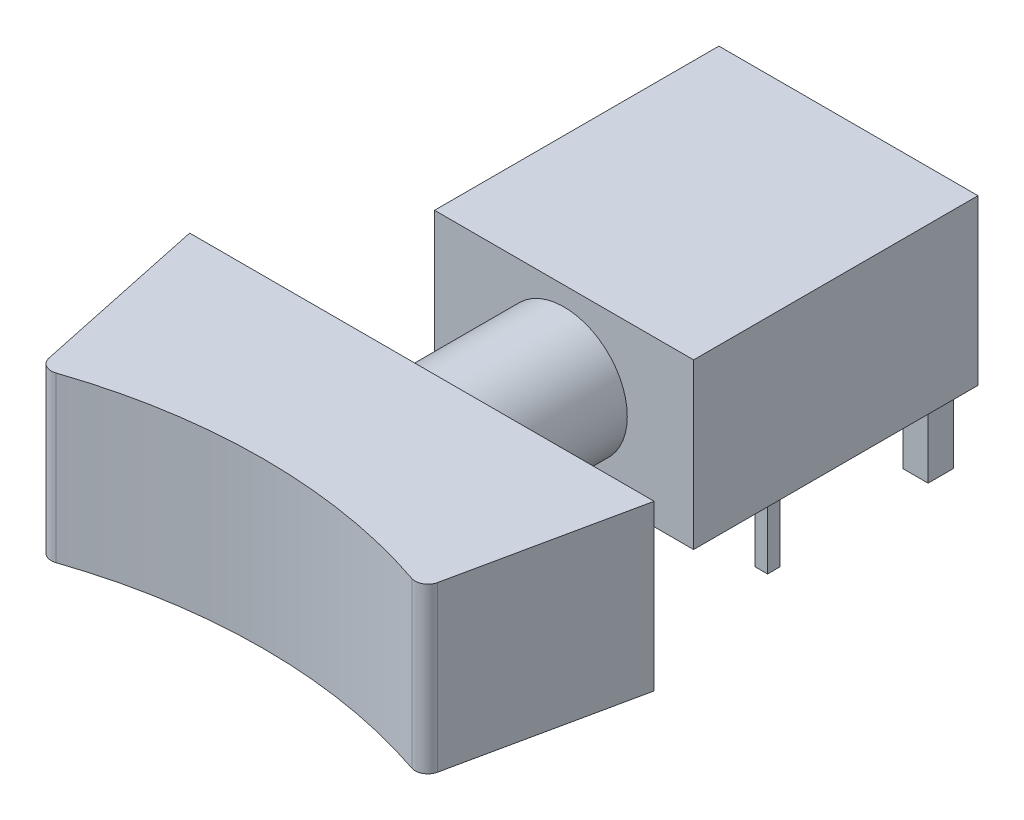
SolidWorks part; units mm, degrees
ref_plane "Front Plane" through (0, 0, 0) normal (0, 0, 1) x (1, 0, 0)
ref_plane "Top Plane" through (0, 0, 0) normal (0, 1, 0) x (1, 0, 0)
ref_plane "Right Plane" through (0, 0, 0) normal (1, 0, 0) x (0, 0, -1)
sketch "Sketch1" plane through (0, 0, 0) normal (0, 1, 0) x (1, 0, 0)
  line L1 (-4.1, 4.5) -> (4.1, 4.5)
  line L2 (-4.1, 4.5) -> (-4.1, -4.5)
  line L3 (-4.1, -4.5) -> (4.1, -4.5)
  line L4 (4.1, 4.5) -> (4.1, -4.5)
  line L5 (-4.1, 4.5) -> (4.1, -4.5) construction
  line L6 (-4.1, -4.5) -> (4.1, 4.5) construction
  point P0 (0, 0)
  dimension "D1" = 9
  dimension "D2" = 8.2
extrude "Boss-Extrude1" add sketch "Sketch1" along normal blind 5.2
sketch "Sketch2" plane through (0, 0, 0) normal (0, -1, 0) x (1, 0, 0)
  line L0 (-2.54, 0.6) -> (2.54, 0.6) construction
  line L1 (-2.74, 0.8) -> (-2.34, 0.8)
  line L2 (-2.74, 0.8) -> (-2.74, 0.4)
  line L3 (-2.74, 0.4) -> (-2.34, 0.4)
  line L4 (-2.34, 0.8) -> (-2.34, 0.4)
  line L5 (-2.74, 0.8) -> (-2.34, 0.4) construction
  line L6 (-2.74, 0.4) -> (-2.34, 0.8) construction
  line L7 (2.34, 0.8) -> (2.74, 0.8)
  line L8 (2.34, 0.8) -> (2.34, 0.4)
  line L9 (2.34, 0.4) -> (2.74, 0.4)
  line L10 (2.74, 0.8) -> (2.74, 0.4)
  line L11 (2.34, 0.8) -> (2.74, 0.4) construction
  line L12 (2.34, 0.4) -> (2.74, 0.8) construction
  line L13 (-2.94, -4.08) -> (-2.14, -4.08)
  line L14 (-2.94, -4.08) -> (-2.94, -4.88)
  line L15 (-2.94, -4.88) -> (-2.14, -4.88)
  line L16 (-2.14, -4.08) -> (-2.14, -4.88)
  line L17 (-2.94, -4.08) -> (-2.14, -4.88) construction
  line L18 (-2.94, -4.88) -> (-2.14, -4.08) construction
  line L19 (-0.4, -4.08) -> (0.4, -4.08)
  line L20 (-0.4, -4.08) -> (-0.4, -4.88)
  line L21 (-0.4, -4.88) -> (0.4, -4.88)
  line L22 (0.4, -4.08) -> (0.4, -4.88)
  line L23 (-0.4, -4.08) -> (0.4, -4.88) construction
  line L24 (-0.4, -4.88) -> (0.4, -4.08) construction
  line L25 (2.14, -4.08) -> (2.94, -4.08)
  line L26 (2.14, -4.08) -> (2.14, -4.88)
  line L27 (2.14, -4.88) -> (2.94, -4.88)
  line L28 (2.94, -4.08) -> (2.94, -4.88)
  line L29 (2.14, -4.08) -> (2.94, -4.88) construction
  line L30 (2.14, -4.88) -> (2.94, -4.08) construction
  line L32 (-4.1, 4.5) -> (4.1, 4.5) construction
  point P0 (-2.54, 0.6)
  point P5 (2.54, 0.6)
  point P10 (-2.54, -4.48)
  point P15 (0, -4.48)
  point P20 (2.54, -4.48)
  point P25 (0, 0.6)
  line M25 (-4.1, -4.5) -> (4.1, -4.5)
  dimension "D1" = 2.54
  dimension "D2" = 2.54
  dimension "D3" = 5.08
  dimension "D4" = 0.8
  dimension "D5" = 0.4
  dimension "D6" = 3.9
  dimension "D7" = 5.08
extrude "Boss-Extrude2" add sketch "Sketch2" along normal blind 3.3
chamfer "Chamfer1" distance 0.1 angle 45 8 edges at (2.54, -3.3, 0.4) (2.34, -3.3, 0.6) (2.54, -3.3, 0.8) (2.74, -3.3, 0.6) (-2.54, -3.3, 0.4) (-2.74, -3.3, 0.6) (-2.54, -3.3, 0.8) (-2.34, -3.3, 0.6)
chamfer "Chamfer2" distance 0.25 angle 45 12 edges at (-2.54, -3.3, -4.88) (-2.94, -3.3, -4.48) (-2.54, -3.3, -4.08) (-2.14, -3.3, -4.48) (0, -3.3, -4.88) (-0.4, -3.3, -4.48) (0, -3.3, -4.08) (0.4, -3.3, -4.48) (2.54, -3.3, -4.88) (2.14, -3.3, -4.48) (2.54, -3.3, -4.08) (2.94, -3.3, -4.48)
extrude "Boss-Extrude3" add sketch "Sketch2<2>" against normal blind 3 contours L16 L14 L15 M25 | L22 L20 L21 M25 | L28 L26 L27 M25 region at (2.54, 0, -4.69) region at (0, 0, -4.69) region at (-2.54, 0, -4.69)
sketch "Sketch2<2>" plane through (0, 0, 0) normal (0, -1, 0) x (1, 0, 0) same geometry as "Sketch2"
fillet "Fillet1" radius 0.3 3 edges at (2.54, 3, -4.88) (0, 3, -4.88) (-2.54, 3, -4.88)
sketch "Sketch3" plane through (0, 0, 4.5) normal (0, 0, 1) x (1, 0, 0)
  line L0 (-4.1, 5.2) -> (-4.1, 0) construction
  circle A0 centre (0, 2.6) radius 2
  point P2 (0, 0)
  point P4 (0, 0)
  point P7 (-4.1, 2.6)
  dimension "D1" = 4
extrude "Boss-Extrude4" add sketch "Sketch3" along normal blind 4.5
sketch "Sketch4" plane through (0, 0, 9) normal (0, 0, 1) x (1, 0, 0)
  line L1 (-7.35, 5.2) -> (7.35, 5.2)
  line L2 (-7.35, 5.2) -> (-7.35, 0)
  line L3 (-7.35, 0) -> (7.35, 0)
  line L4 (7.35, 5.2) -> (7.35, 0)
  line L5 (-7.35, 5.2) -> (7.35, 0) construction
  line L6 (-7.35, 0) -> (7.35, 5.2) construction
  point P0 (0, 2.6)
  dimension "D1" = 5.2
  dimension "D2" = 14.7
extrude "Boss-Extrude5" add sketch "Sketch4" along normal offset from surface (6.1 mm away) 10.6 up to face at (2, 2.6, 4.5) offset beyond the face yes
sketch "Sketch5" plane through (0, 5.2, 0) normal (0, 1, 0) x (1, 0, 0)
  line L1 (-7.35, -9) -> (-6.0568, -15.1)
  line L2 (6.0568, -15.1) -> (7.35, -9)
  line L3 (-7.35, -15.1) -> (7.35, -15.1) construction
  line L4 (7.35, -9) -> (7.35, -15.1)
  line L5 (7.35, -15.1) -> (6.0568, -15.1)
  line L6 (-7.35, -9) -> (-7.35, -15.1)
  line L7 (-7.35, -15.1) -> (-6.0568, -15.1)
  line L8 (6.0568, -15.1) -> (-6.0568, -15.1)
  arc A0 (-6.0568, -15.1) -> (6.0568, -15.1) centre (0, -31.5536) cw
  point P3 (0, -14.0206)
  line M4 (-7.35, -9) -> (-7.35, -15.1)
  line M5 (-7.35, -15.1) -> (7.35, -15.1)
  line M6 (7.35, -15.1) -> (7.35, -9)
extrude "Cut-Extrude1" cut sketch "Sketch5" against normal through all contours L1 M4 M5 | A0 M5 | L2 M5 M6 region at (6.9189, 5.2, 13.0667) region at (0, 5.2, 14.6671) region at (-6.9189, 5.2, 13.0667)
fillet "Fillet2" radius 0.4 2 edges at (-6.0568, 2.6, 15.1) (6.0568, 2.6, 15.1)
